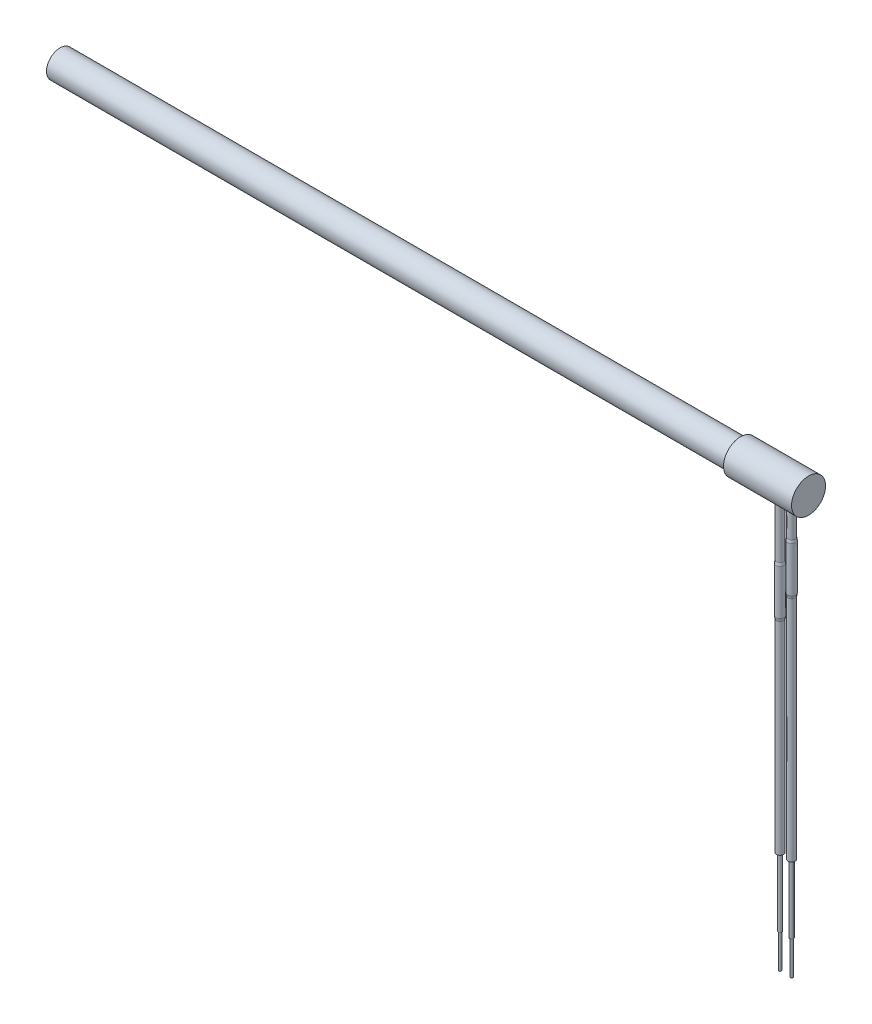
SolidWorks part; units mm, degrees
note: '?' marks a value the reader was unsure of.
ref_plane "Front Plane" through (0, 0, 0) normal (0, 0, 1) x (1, 0, 0)
ref_plane "Top Plane" through (0, 0, 0) normal (0, 1, 0) x (1, 0, 0)
ref_plane "Right Plane" through (0, 0, 0) normal (1, 0, 0) x (0, 0, -1)
ref_axis "Axis1" through (0, 0, 0) along (1, 0, 0)?
sketch "Sketch1" plane through (0, 0, 0) normal (0, 0, 1) x (1, 0, 0)
  line L0 (0, 4) -> (0, 5)
  line L1 (-200, 0) -> (20, 0) construction
  line L2 (20, 0) -> (20, 5)
  line L3 (0, 4) -> (-200, 4)
  line L4 (-200, 0) -> (-200, 4)
  line L6 (0, 5) -> (20, 5)
  line L10 (20, -5) -> (11.63, -5) construction
  line L12 (13.33, 5) -> (13.33, -95) construction
  line L13 (15.03, 0) -> (15.03, -95) construction
  line L14 (11.63, 0) -> (11.63, -95) construction
  line L15 (15.03, -95) -> (11.63, -95) construction
  line L16 (20, 0) -> (20, -5) construction
  line L17 (-200, 0) -> (20, 0)
  dimension "L" = 200
  dimension "FIX_1" = 20
  dimension "KSS_1" = 10
  dimension "D" = 8
  dimension "FIX_3" = 13.33
  dimension "FIX_2" = 90
  dimension "FIX_4" = 3.4
revolve "Revolve1" add sketch "Sketch1" about L1
sketch "Sketch2" plane through (0, 0, 0) normal (0, 0, 1) x (1, 0, 0)
  line L0 (15.03, 0) -> (15.03, -125) construction
  line L2 (20, -5) -> (11.63, -5) construction
  line L3 (15.405, -125) -> (15.405, -115)
  line L5 (15.405, -115) -> (15.58, -115)
  line L6 (15.58, -115) -> (15.58, -95)
  line L7 (15.58, -95) -> (16.08, -95)
  line L14 (15.03, 0) -> (15.03, -125)
  line L15 (15.03, 0) -> (16.08, 0)
  line L16 (15.03, -125) -> (15.405, -125)
  line L17 (15.03, 0) -> (15.03, -95) construction
  line L18 (16.08, -95) -> (16.08, 0)
  line L19 (16.11, -5) -> (15.03, -5) construction
  dimension "FIX_5" = 20
  dimension "KSS_4" = 0.75
  dimension "KSS_3" = 1.1
  dimension "FIX_6" = 10
  dimension "KSS_2" = 2.1
  dimension "FIX_2" = 90
revolve "Revolve2" add sketch "Sketch2" about L0
pattern_linear "LPattern1" count 2 spacing 3.4 along (-1, 0, 0) of "Revolve2"
sketch "Sketch3" plane through (0, 0, 0) normal (0, 0, 1) x (1, 0, 0)
  line L0 (15.03, -13) -> (15.03, -28) construction
  line L2 (16.23, -20.5) -> (15.03, -20.5) construction
  line L3 (15.03, -13) -> (16.08, -13)
  line L6 (16.08, -28) -> (15.03, -28)
  line L11 (16.08, -13) -> (16.23, -13.8507)
  line L12 (16.23, -13.8507) -> (16.23, -27.1493)
  line L13 (16.23, -27.1493) -> (16.08, -28)
  line L14 (15.03, 0) -> (15.03, -95) construction
  line L15 (20, -5) -> (11.63, -5) construction
  line L18 (15.03, -13) -> (15.03, -28)
  dimension "KSS_6" = 2.4
  dimension "KSS_5" = 2.1
  dimension "FIX_8" = 15.5
  dimension "FIX_9" = 15
  dimension "FIX_11" = 10
revolve "Revolve3" add sketch "Sketch3" about L0
sketch "Sketch4" plane through (0, 0, 0) normal (0, 0, 1) x (1, 0, 0)
  line L0 (11.63, -20.5) -> (11.63, -35.5) construction
  line L2 (12.83, -28) -> (11.63, -28) construction
  line L3 (11.63, -20.5) -> (12.68, -20.5)
  line L6 (12.68, -35.5) -> (11.63, -35.5)
  line L11 (12.68, -20.5) -> (12.83, -21.3507)
  line L12 (12.83, -21.3507) -> (12.83, -34.6493)
  line L13 (12.83, -34.6493) -> (12.68, -35.5)
  line L15 (11.63, -20.5) -> (11.63, -35.5)
  line L17 (11.63, 0) -> (11.63, -95) construction
  line L18 (20, -5) -> (11.63, -5) construction
  dimension "KSS_7" = 2.1
  dimension "KSS_8" = 2.4
  dimension "FIX_12" = 23
  dimension "FIX_9" = 15
  dimension "FIX_11" = 10
revolve "Revolve4" add sketch "Sketch4" about L0
equation "\"ANGLE360\"= 360"
equation "\"KSS_1@Sketch1\"= \"D@Sketch1\" + 2"
equation "\"KSS_2@Sketch2\" = if ( \"D@Sketch1\" = > 8 , 2.1 , 2.5 )"
equation "\"KSS_3@Sketch2\" = if ( \"D@Sketch1\" = > 8 , 1.1 , 1.5 )"
equation "\"KSS_4@Sketch2\" = if ( \"D@Sketch1\" = > 8 , 0.75 , 1.25 )"
equation "\"KSS_5@Sketch3\" = \"KSS_2@Sketch2\""
equation "\"KSS_6@Sketch3\" = \"KSS_5@Sketch3\" + 0.3"
equation "\"KSS_7@Sketch4\" = \"KSS_2@Sketch2\""
equation "\"KSS_8@Sketch4\"= \"KSS_2@Sketch2\" + 0.3"
